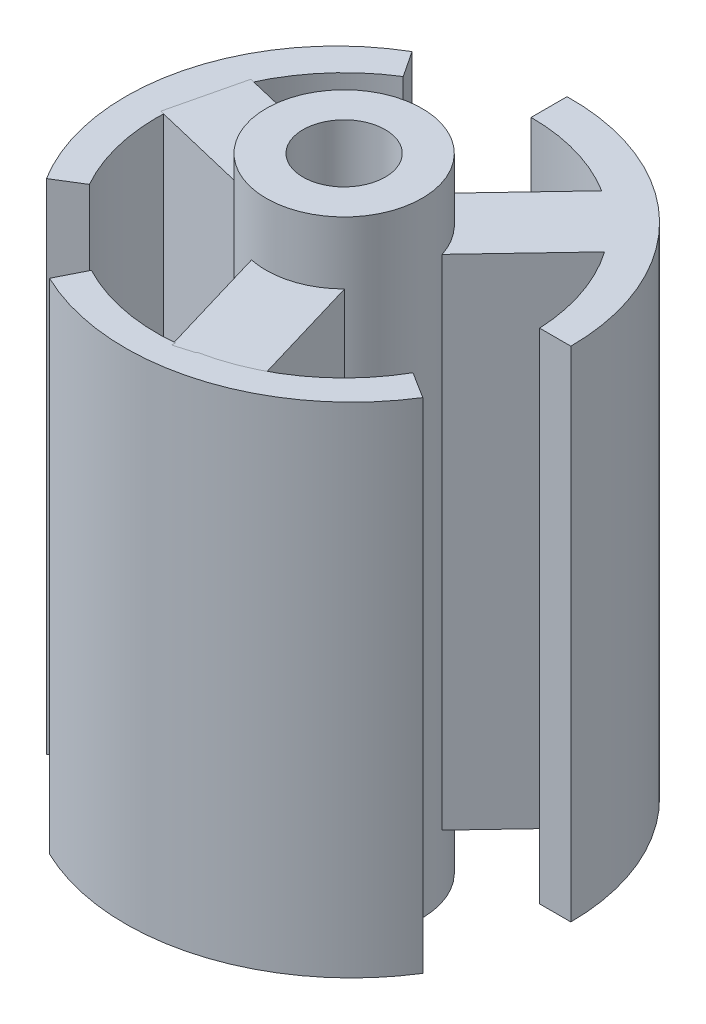
SolidWorks part; units mm, degrees
ref_plane "Front Plane" through (0, 0, 0) normal (0, 0, 1) x (1, 0, 0)
ref_plane "Top Plane" through (0, 0, 0) normal (0, 1, 0) x (1, 0, 0)
ref_plane "Right Plane" through (0, 0, 0) normal (1, 0, 0) x (0, 0, -1)
sketch "Sketch11" plane through (0, 0, 0) normal (0, 1, 0) x (1, 0, 0)
  line L0 (-15.1905, -8.6889) -> (0, 0.7002)
  line L1 (0, 0.7002) -> (-8.1366, -15.4934)
  line L2 (15.1201, -8.8109) -> (0, 0.7002)
  line L3 (0, 0.7002) -> (17.486, 0.7002)
  line L4 (0, 0.7002) -> (-9.3494, 14.7932)
  line L5 (0, 0.7002) -> (0, 17.8816)
  arc A3 (15.1201, -8.8109) -> (-8.1366, -15.4934) centre (-0.2456, 0.8547) cw
  arc A5 (-15.1905, -8.6889) -> (-9.3494, 14.7932) centre (-0.8078, 0.2009) cw
  arc A6 (17.486, 0.7002) -> (0, 17.8816) centre (0.3019, 0.7002) ccw
  point P11 (0, 0)
  point P12 (0, 0)
sketch "Sketch12" plane through (0, 0, 0) normal (0, 1, 0) x (1, 0, 0)
  circle A0 centre (0, 0) radius 15
extrude "Boss-Extrude6" add sketch "Sketch11" along normal blind 40 contours L0 A5 L4 | L2 A3 L1 | L3 A6 L5
extrude "Cut-Extrude9" cut sketch "Sketch12" along normal blind 40 contours A0
sketch "Sketch17" plane through (0, 0, 0) normal (0, 1, 0) x (1, 0, 0)
  line L0 (12.4951, 8.8245) -> (8.1399, 12.9515)
  line L1 (12.4951, 8.8245) -> (2.1256, -2.1183)
  line L2 (8.1399, 12.9515) -> (-2.2296, 2.0087)
  line L3 (2.1256, -2.1183) -> (-2.2296, 2.0087)
  line L4 (-2.8974, -0.7817) -> (2.8543, 0.9265)
  line L5 (1.3947, -15.2333) -> (-2.8974, -0.7817)
  line L6 (1.3947, -15.2333) -> (7.1464, -13.5251)
  line L7 (7.1464, -13.5251) -> (2.8543, 0.9265)
  line L8 (0.7717, 2.9) -> (-0.6248, -2.9352)
  line L9 (-13.8898, 6.4089) -> (0.7717, 2.9)
  line L10 (-13.8898, 6.4089) -> (-15.2863, 0.5736)
  line L11 (-15.2863, 0.5736) -> (-0.6248, -2.9352)
  arc A1 (14.9836, 0.7002) -> (0, 15) centre (0, 0) ccw construction
  point P18 (0, 0)
  dimension "D1" = 3
extrude "Boss-Extrude8" add sketch "Sketch17" along normal blind 40 separate body contours L2 L9 L8 L4 L7 L1 L0 | L4 L8 L3 L1 L7 | L9 L2 L3 L4 L8 | L11 L5 L6 L7 L1 L3 L8 | L5 L11 L8 L3 L4 | L10 L11 L5 L4 L3 L2 L9 | L4 L7 L6 L5 region at (5.7685, 0, -6.0874) region at (2.3876, 0, 8.0393) region at (1.914, 0, 0.4581) region at (-0.5603, 0, -1.8866) region at (-8.1561, 0, -1.9519) region at (-1.3537, 0, 1.4286)
sketch "Sketch18" plane through (0, 0, 0) normal (0, 1, 0) x (1, 0, 0)
  circle A0 centre (0, 0) radius 6.25
extrude "Boss-Extrude9" add sketch "Sketch18" along normal blind 45
extrude "Boss-Extrude10" add sketch "Sketch18<2>" against normal blind 5
sketch "Sketch18<2>" plane through (0, 0, 0) normal (0, 1, 0) x (1, 0, 0) same geometry as "Sketch18"
ref_plane "Plane1" through (0, -5, 0) normal (0, -1, 0) x (-1, 0, 0)
sketch "Sketch19" plane through (0, -5, 0) normal (0, -1, 0) x (-1, 0, 0)
  circle A0 centre (0, 0) radius 3.3
extrude "Cut-Extrude10" cut sketch "Sketch19" against normal blind 50
